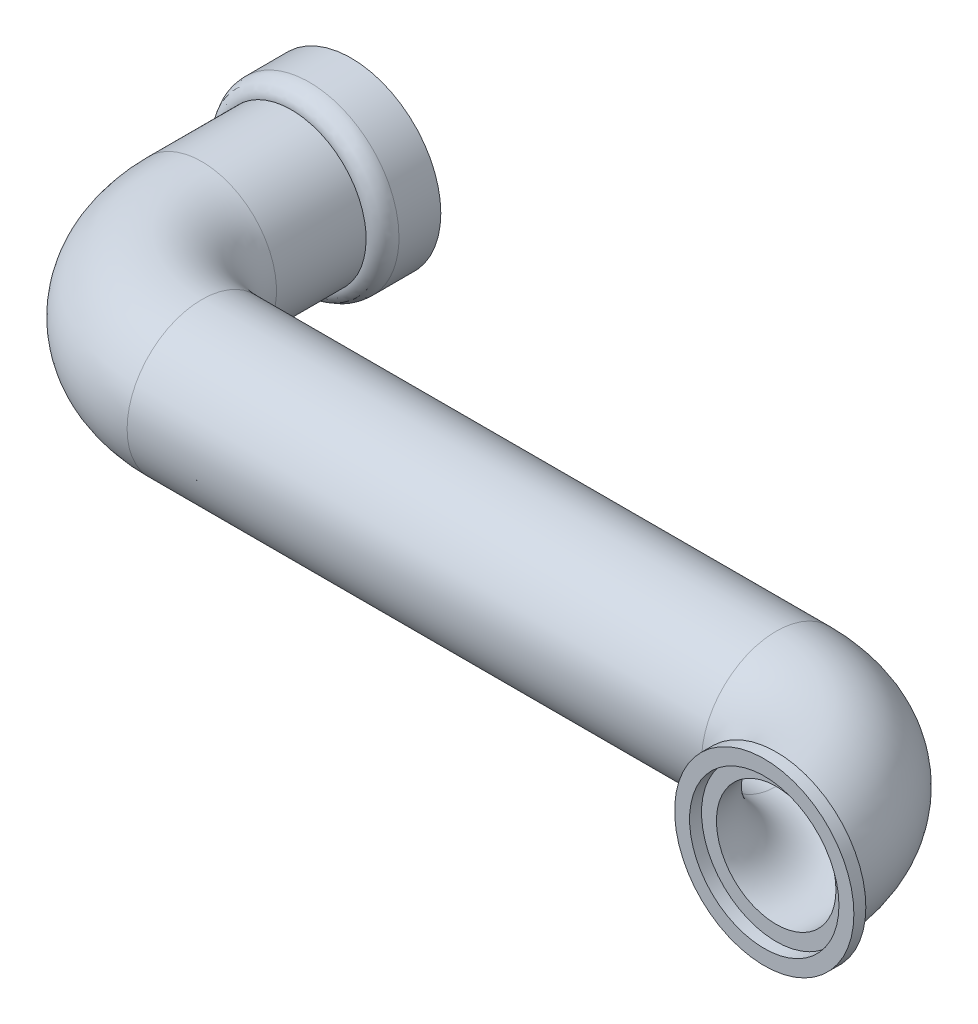
SolidWorks part; units mm, degrees
ref_plane "Alzado" through (0, 0, 0) normal (0, 0, 1) x (1, 0, 0)
ref_plane "Planta" through (0, 0, 0) normal (0, 1, 0) x (1, 0, 0)
ref_plane "Vista lateral" through (0, 0, 0) normal (1, 0, 0) x (0, 0, -1)
sketch "Croquis1" plane through (0, 0, 0) normal (0, 0, 1) x (1, 0, 0)
  circle A0 centre (0, 0) radius 12.5
  circle A1 centre (0, 0) radius 15
extrude "Saliente-Extruir1" add sketch "Croquis1" along normal blind 10
sketch "Croquis2" plane through (0, 0, 10) normal (0, 0, 1) x (1, 0, 0)
  circle A0 centre (0, 0) radius 12.5
  circle A1 centre (0, 0) radius 10
extrude "Saliente-Extruir2" add sketch "Croquis2" along normal blind 15 separate body
fillet "Redondeo3" radius 3 1 edges at (15, 0, 10) second distance 2.5 first distance on face at (15, 0, 10)
sketch "Croquis3" plane through (0, 0, 10) normal (0, 0, -1) x (-1, 0, 0)
  circle A0 centre (0, 0) radius 10
  circle A1 centre (0, 0) radius 12.5
extrude "Saliente-Extruir3" add sketch "Croquis3" along normal blind 1
sketch "Croquis5" plane through (0, 0, 0) normal (0, 1, 0) x (1, 0, 0)
  line L1 (-12.5, -25) -> (12.5, -25) construction
  line L3 (20, -45) -> (116.13, -45)
  arc A0 (0, -25) -> (20, -45) centre (20, -25) ccw
  arc A1 (116.13, -45) -> (136.13, -65) centre (116.13, -65) cw
sketch "Croquis6" plane through (0, 0, 25) normal (0, 0, 1) x (1, 0, 0)
  circle A0 centre (0, 0) radius 10
  circle A1 centre (0, 0) radius 12.5
sweep "Barrer1" add profiles "Croquis6" path "Croquis5"
sketch "Croquis7" plane through (0, 0, 65) normal (0, 0, 1) x (1, 0, 0)
  line L0 (136.13, 0) -> (116.13, 0) construction
  circle A0 centre (136.13, 0) radius 12.5
  circle A1 centre (136.13, 0) radius 15
extrude "Saliente-Extruir4" add sketch "Croquis7" along normal blind 2 separate body
